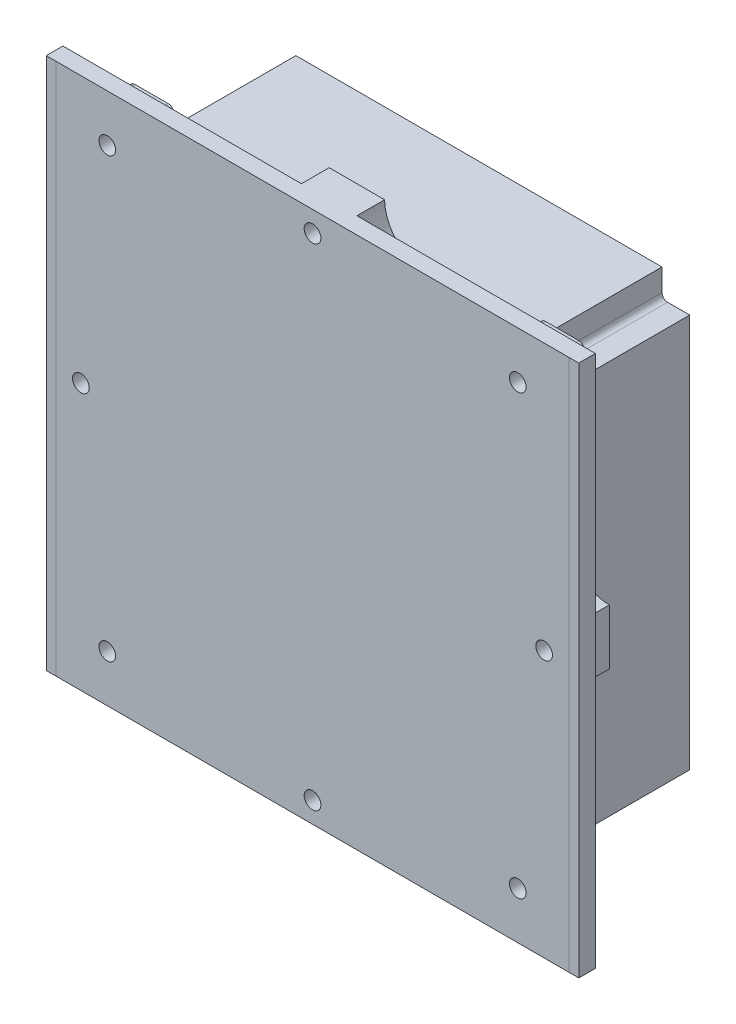
SolidWorks part; units mm, degrees
material "6061-T4 (SS)"
ref_plane "Front Plane" through (0, 0, 0) normal (0, 0, 1) x (1, 0, 0)
ref_plane "Top Plane" through (0, 0, 0) normal (0, 1, 0) x (1, 0, 0)
ref_plane "Right Plane" through (0, 0, 0) normal (1, 0, 0) x (0, 0, -1)
sketch "Sketch2" plane through (0, 0, 0) normal (0, 0, 1) x (1, 0, 0)
  line L1 (-48, 48) -> (48, 48)
  line L2 (-48, 48) -> (-48, -48)
  line L3 (-48, -48) -> (48, -48)
  line L4 (48, 48) -> (48, -48)
  point P4 (-48, 0)
  point P6 (0, -48)
  dimension "D1" = 96
extrude "Boss-Extrude1" add sketch "Sketch2" against normal blind 3 contours L1 L4 L3 L2
sketch "Sketch6" plane through (0, 0, -3) normal (0, 0, -1) x (-1, 0, 0)
  line L5 (-46.25, 48) -> (-46.25, -48)
  line L6 (-46.25, 48) -> (-46.25, -48)
  line L8 (46.25, 48) -> (46.25, -48)
  line L9 (46.25, 48) -> (46.25, -48)
  dimension "D1" = 1.75
  dimension "D2" = 1.75
split line "Split Line1"
sketch "Sketch3" plane through (0, 0, -3) normal (0, 0, -1) x (-1, 0, 0)
  line L0 (-35, 22.5) -> (-35, -22.5)
  line L1 (-20, -37.5) -> (20, -37.5)
  line L2 (35, 22.5) -> (35, -22.5)
  line L3 (-20, 37.5) -> (20, 37.5)
  line L4 (-31, -40.5) -> (31, -40.5)
  line L5 (38, 33.5) -> (38, -33.5)
  line L7 (-38, 33.5) -> (-38, -33.5)
  line L8 (-31, 40.5) -> (31, 40.5)
  line L9 (40, -35.5) -> (41.6953, -35.5) construction
  line L10 (33, -43.5) -> (41, -43.5)
  line L13 (41, -43.5) -> (41, -35.5)
  line L14 (35, -43.5) -> (41, -37.5) construction
  line L15 (0, 0) -> (0, -68.5412) construction
  line L16 (33, -42.5) -> (33, -44.6955) construction
  line L17 (0, 0) -> (-81.2569, 0) construction
  line L18 (40, -35.5) -> (41, -35.5)
  line L19 (33, -43.5) -> (33, -42.5)
  line L20 (38, -33.5) -> (38, -40.5) construction
  line L21 (38, -40.5) -> (31, -40.5) construction
  line L22 (-40, -35.5) -> (-41, -35.5)
  line L23 (-41, -43.5) -> (-41, -35.5)
  line L24 (-33, -43.5) -> (-41, -43.5)
  line L25 (-33, -43.5) -> (-33, -42.5)
  line L26 (40, 35.5) -> (41, 35.5)
  line L27 (41, 43.5) -> (41, 35.5)
  line L28 (33, 43.5) -> (41, 43.5)
  line L29 (33, 43.5) -> (33, 42.5)
  line L30 (-40, 35.5) -> (-41, 35.5)
  line L31 (-41, 43.5) -> (-41, 35.5)
  line L32 (-33, 43.5) -> (-41, 43.5)
  line L33 (-33, 43.5) -> (-33, 42.5)
  line L34 (-46.25, 48) -> (-46.25, -48) construction
  line L35 (46.25, 48) -> (-46.25, 48) construction
  arc A0 (-20, 37.5) -> (-35, 22.5) centre (-20, 22.5) ccw
  arc A1 (-20, -37.5) -> (-35, -22.5) centre (-20, -22.5) cw
  arc A2 (20, -37.5) -> (35, -22.5) centre (20, -22.5) ccw
  arc A3 (35, 22.5) -> (20, 37.5) centre (20, 22.5) ccw
  arc A6 (38, -33.5) -> (40, -35.5) centre (40, -33.5) ccw
  arc A7 (31, -40.5) -> (33, -42.5) centre (31, -42.5) cw
  arc A8 (-38, -33.5) -> (-40, -35.5) centre (-40, -33.5) cw
  arc A9 (-31, -40.5) -> (-33, -42.5) centre (-31, -42.5) ccw
  arc A10 (38, 33.5) -> (40, 35.5) centre (40, 33.5) cw
  arc A11 (31, 40.5) -> (33, 42.5) centre (31, 42.5) ccw
  arc A12 (-38, 33.5) -> (-40, 35.5) centre (-40, 33.5) ccw
  arc A13 (-31, 40.5) -> (-33, 42.5) centre (-31, 42.5) cw
  point P8 (0, -37.5)
  point P9 (0, 37.5)
  point P11 (-35, 0)
  point P12 (35, 0)
  dimension "D1" = 15
  dimension "D10" = 2
  dimension "D3" = 76
  dimension "D2" = 3
  dimension "D4" = 75
  dimension "D6" = 3
  dimension "D8" = 8
  dimension "D9" = 8
  dimension "D11" = 43.5
  dimension "D12" = 41
extrude "Boss-Extrude2" add sketch "Sketch3" along normal blind 27 contours L7 L5 L8
sketch "Sketch15" plane through (0, 0, -3) normal (0, 0, -1) x (-1, 0, 0)
  line L1 (46.25, 48) -> (-46.25, 48) construction
  line L2 (-5, 48) -> (5, 48)
  line L5 (31, 40.5) -> (-31, 40.5) construction
  line L6 (-12.5, 40.5) -> (12.5, 40.5)
  line L17 (45.5, 5) -> (45.5, -5)
  line L19 (38, 12.5) -> (38, -12.5)
  line L21 (5, -48) -> (-5, -48)
  line L23 (12.5, -40.5) -> (-12.5, -40.5)
  line L25 (-45.5, -5) -> (-45.5, 5)
  line L27 (-38, -12.5) -> (-38, 12.5)
  line L31 (38, -33.5) -> (38, 33.5) construction
  line L32 (-31, -40.5) -> (31, -40.5) construction
  line L34 (-38, 33.5) -> (-38, -33.5) construction
  arc A0 (5, 48) -> (12.5, 40.5) centre (12.5, 48) ccw
  arc A1 (-5, 48) -> (-12.5, 40.5) centre (-12.5, 48) cw
  arc A2 (45.5, 5) -> (38, 12.5) centre (45.5, 12.5) cw
  arc A7 (45.5, -5) -> (38, -12.5) centre (45.5, -12.5) ccw
  arc A14 (5, -48) -> (12.5, -40.5) centre (12.5, -48) cw
  arc A15 (-5, -48) -> (-12.5, -40.5) centre (-12.5, -48) ccw
  arc A23 (-38, 12.5) -> (-45.5, 5) centre (-45.5, 12.5) cw
  arc A25 (-38, -12.5) -> (-45.5, -5) centre (-45.5, -12.5) ccw
  point P6 (0, 40.5)
  point P17 (-38, 0)
  point P54 (38, 0)
  point P61 (0, -40.5)
  dimension "D2" = 10
  dimension "D5" = 7.5
  dimension "D6" = 10
  dimension "D8" = 7.5
  dimension "D11" = 7.5
extrude "Boss-Extrude6" add sketch "Sketch15" along normal blind 5
sketch "Sketch18" plane through (0, 0, 0) normal (0, 0, 1) x (1, 0, 0)
  line L0 (-5, 48) -> (5, 48) construction
  line L2 (-45.5, -5) -> (-45.5, 5) construction
  line L3 (45.5, 5) -> (45.5, -5) construction
  line L4 (5, -48) -> (-5, -48) construction
  circle A0 centre (0, 44.25) radius 1.5
  circle A1 centre (0, -44.25) radius 1.5
  circle A3 centre (41.75, 0) radius 1.5
  circle A7 centre (-41.75, 0) radius 1.5
  point P20 (0, 48)
  point P23 (45.5, 0)
  point P28 (-45.5, 0)
  point P30 (0, -48)
  dimension "D1" = 3
  dimension "D2" = 3.75
  dimension "D3" = 3.75
  dimension "D4" = 3.75
  dimension "D5" = 3.75
extrude "Cut-Extrude3" cut sketch "Sketch18" against normal through all contours A0
sketch "Sketch16" plane through (0, 0, -3) normal (0, 0, -1) x (-1, 0, 0)
  line L1 (-35, 22.5) -> (-30, 22.5)
  line L2 (-35, 22.5) -> (-35, 13)
  line L3 (-35, 13) -> (-30, 13)
  line L4 (-30, 22.5) -> (-30, 13)
  line L5 (30, 22.5) -> (35, 22.5)
  line L6 (30, 22.5) -> (30, 13)
  line L7 (30, 13) -> (35, 13)
  line L8 (35, 22.5) -> (35, 13)
  dimension "D1" = 9.5
  dimension "D2" = 5
  dimension "D3" = 5
extrude "Boss-Extrude7" add sketch "Sketch16" along normal blind 15 contours L4 L3 L2 L1
sketch "Sketch17" plane through (0, 0, -18) normal (0, 0, -1) x (-1, 0, 0)
  line L0 (-30, 13) -> (-30, 22.5) construction
  line L1 (-35, 13) -> (-30, 13) construction
  line L2 (30, 13) -> (35, 13) construction
  line L3 (30, 22.5) -> (30, 13) construction
  circle A0 centre (-32.5, 17.75) radius 1.5
  circle A1 centre (32.5, 17.75) radius 1.5
  point P7 (-30, 17.75)
  point P11 (-32.5, 13)
  point P15 (32.5, 13)
  point P18 (30, 17.75)
  dimension "D1" = 3
extrude "Cut-Extrude2" cut sketch "Sketch17" against normal blind 3.175 contours A0
fillet "Fillet2" radius 1 12 edges at (-33, 43.5, -16.5) (-41, 35.5, -16.5) (-41, 43.5, -16.5) (33, 43.5, -16.5) (41, 43.5, -16.5) (41, 35.5, -16.5) (41, -35.5, -16.5) (33, -43.5, -16.5) (-33, -43.5, -16.5) (-41, -35.5, -16.5) (-41, -43.5, -16.5) (41, -43.5, -16.5)
sketch "Sketch22" plane through (0, 0, 0) normal (0, 0, 1) x (1, 0, 0)
  line L0 (41, 42.5) -> (41, 36.5) construction
  line L1 (34, 43.5) -> (40, 43.5) construction
  line L2 (41, 42.5) -> (41, 36.5) construction
  line L3 (34, 43.5) -> (40, 43.5) construction
  line L4 (33.2929, 43.2071) -> (40.7071, 35.7929) construction
  line L5 (0, 0) -> (0, 60.4254) construction
  line L6 (0, 0) -> (75.1466, 0) construction
  arc A0 (31, 40.5) -> (33, 42.5) centre (31, 42.5) ccw construction
  arc A1 (34, 43.5) -> (33, 42.5) centre (34, 42.5) ccw construction
  arc A2 (40, 35.5) -> (38, 33.5) centre (40, 33.5) ccw construction
  arc A3 (40, 35.5) -> (41, 36.5) centre (40, 36.5) ccw construction
  arc A4 (41, 42.5) -> (40, 43.5) centre (40, 42.5) ccw construction
  arc A5 (31, 40.5) -> (33, 42.5) centre (31, 42.5) ccw construction
  arc A6 (34, 43.5) -> (33, 42.5) centre (34, 42.5) ccw construction
  arc A7 (40, 35.5) -> (38, 33.5) centre (40, 33.5) ccw construction
  arc A8 (40, 35.5) -> (41, 36.5) centre (40, 36.5) ccw construction
  arc A9 (41, 42.5) -> (40, 43.5) centre (40, 42.5) ccw construction
  circle A10 centre (37, 39.5) radius 1.5
  circle A11 centre (-37, 39.5) radius 1.5
  circle A12 centre (37, -39.5) radius 1.5
  circle A13 centre (-37, -39.5) radius 1.5
  dimension "D1" = 3
extrude "Cut-Extrude5" cut sketch "Sketch22" against normal through all
sketch "Sketch23" plane through (0, 0, -30) normal (0, 0, -1) x (-1, 0, 0)
  line L0 (-40.7071, -43.2071) -> (-32.5482, -35.0482) construction
  line L1 (-40, -35.5) -> (-34, -35.5)
  line L2 (-33, -36.5) -> (-33, -42.5)
  line L3 (-41, -36.5) -> (-41, -42.5) construction
  line L4 (-40, -43.5) -> (-34, -43.5) construction
  line L5 (-41, -36.5) -> (-41, -42.5)
  line L6 (-40, -43.5) -> (-34, -43.5)
  line L7 (0, 0) -> (0, -60.8456) construction
  line L8 (0, 0) -> (68.1956, 0) construction
  line L9 (-41, -42.5) -> (-41, -36.5)
  line L10 (-34, -43.5) -> (-40, -43.5)
  line L11 (-34, -35.5) -> (-40, -35.5)
  line L12 (-33, -42.5) -> (-33, -36.5)
  line L13 (40.7071, -43.2071) -> (32.5482, -35.0482) construction
  line L14 (33, -42.5) -> (33, -36.5)
  line L15 (34, -35.5) -> (40, -35.5)
  line L16 (34, -43.5) -> (40, -43.5)
  line L17 (41, -42.5) -> (41, -36.5)
  line L18 (40, -43.5) -> (34, -43.5)
  line L19 (41, -36.5) -> (41, -42.5)
  line L20 (33, -36.5) -> (33, -42.5)
  line L21 (40, -35.5) -> (34, -35.5)
  line L22 (40.7071, 43.2071) -> (32.5482, 35.0482) construction
  line L23 (40, 35.5) -> (34, 35.5)
  line L24 (33, 36.5) -> (33, 42.5)
  line L25 (41, 36.5) -> (41, 42.5)
  line L26 (40, 43.5) -> (34, 43.5)
  line L27 (41, 42.5) -> (41, 36.5)
  line L28 (34, 43.5) -> (40, 43.5)
  line L29 (34, 35.5) -> (40, 35.5)
  line L30 (33, 42.5) -> (33, 36.5)
  line L31 (-40.7071, 43.2071) -> (-32.5482, 35.0482) construction
  line L32 (-33, 42.5) -> (-33, 36.5)
  line L33 (-34, 35.5) -> (-40, 35.5)
  line L34 (-34, 43.5) -> (-40, 43.5)
  line L35 (-41, 42.5) -> (-41, 36.5)
  line L36 (-40, 43.5) -> (-34, 43.5)
  line L37 (-41, 36.5) -> (-41, 42.5)
  line L38 (-33, 36.5) -> (-33, 42.5)
  line L39 (-40, 35.5) -> (-34, 35.5)
  arc A0 (-41, -42.5) -> (-40, -43.5) centre (-40, -42.5) ccw construction
  arc A1 (-40, -35.5) -> (-41, -36.5) centre (-40, -36.5) ccw construction
  arc A2 (-34, -43.5) -> (-33, -42.5) centre (-34, -42.5) ccw construction
  arc A3 (-40, -35.5) -> (-41, -36.5) centre (-40, -36.5) ccw
  arc A4 (-41, -42.5) -> (-40, -43.5) centre (-40, -42.5) ccw
  arc A5 (-34, -43.5) -> (-33, -42.5) centre (-34, -42.5) ccw
  arc A6 (-34, -35.5) -> (-33, -36.5) centre (-34, -36.5) cw
  arc A7 (-41, -36.5) -> (-40, -35.5) centre (-40, -36.5) cw
  arc A8 (-33, -42.5) -> (-34, -43.5) centre (-34, -42.5) cw
  arc A9 (33, -42.5) -> (34, -43.5) centre (34, -42.5) ccw
  arc A10 (41, -36.5) -> (40, -35.5) centre (40, -36.5) ccw
  arc A11 (34, -35.5) -> (33, -36.5) centre (34, -36.5) ccw
  arc A12 (34, -43.5) -> (33, -42.5) centre (34, -42.5) cw
  arc A13 (41, -42.5) -> (40, -43.5) centre (40, -42.5) cw
  arc A14 (40, -35.5) -> (41, -36.5) centre (40, -36.5) cw
  arc A15 (40, 35.5) -> (41, 36.5) centre (40, 36.5) ccw
  arc A16 (41, 42.5) -> (40, 43.5) centre (40, 42.5) ccw
  arc A17 (34, 43.5) -> (33, 42.5) centre (34, 42.5) ccw
  arc A18 (34, 35.5) -> (33, 36.5) centre (34, 36.5) cw
  arc A19 (41, 36.5) -> (40, 35.5) centre (40, 36.5) cw
  arc A20 (33, 42.5) -> (34, 43.5) centre (34, 42.5) cw
  arc A21 (-33, 42.5) -> (-34, 43.5) centre (-34, 42.5) ccw
  arc A22 (-41, 36.5) -> (-40, 35.5) centre (-40, 36.5) ccw
  arc A23 (-34, 35.5) -> (-33, 36.5) centre (-34, 36.5) ccw
  arc A24 (-34, 43.5) -> (-33, 42.5) centre (-34, 42.5) cw
  arc A25 (-41, 42.5) -> (-40, 43.5) centre (-40, 42.5) cw
  arc A26 (-40, 35.5) -> (-41, 36.5) centre (-40, 36.5) cw
  point P16 (-33, -35.5)
  point P35 (33, -35.5)
  point P50 (33, 35.5)
  point P65 (-33, 35.5)
  circle M6 centre (37, 39.5) radius 1.5
  circle M7 centre (-37, -39.5) radius 1.5
  circle M8 centre (37, -39.5) radius 1.5
  circle M9 centre (-37, 39.5) radius 1.5
  line M10 (40, 43.5) -> (34, 43.5)
  arc M11 (34, 43.5) -> (33, 42.5) centre (34, 42.5) ccw
  arc M15 (-33, 42.5) -> (-34, 43.5) centre (-34, 42.5) ccw
  line M16 (-34, 43.5) -> (-40, 43.5)
  arc M17 (-40, 43.5) -> (-41, 42.5) centre (-40, 42.5) ccw
  line M18 (-41, 42.5) -> (-41, 36.5)
  arc M19 (-41, 36.5) -> (-40, 35.5) centre (-40, 36.5) ccw
  arc M23 (-40, -35.5) -> (-41, -36.5) centre (-40, -36.5) ccw
  line M24 (-41, -36.5) -> (-41, -42.5)
  arc M25 (-41, -42.5) -> (-40, -43.5) centre (-40, -42.5) ccw
  line M26 (-40, -43.5) -> (-34, -43.5)
  arc M27 (-34, -43.5) -> (-33, -42.5) centre (-34, -42.5) ccw
  arc M31 (33, -42.5) -> (34, -43.5) centre (34, -42.5) ccw
  line M32 (34, -43.5) -> (40, -43.5)
  arc M33 (40, -43.5) -> (41, -42.5) centre (40, -42.5) ccw
  line M34 (41, -42.5) -> (41, -36.5)
  arc M35 (41, -36.5) -> (40, -35.5) centre (40, -36.5) ccw
  arc M39 (40, 35.5) -> (41, 36.5) centre (40, 36.5) ccw
  line M40 (41, 36.5) -> (41, 42.5)
  arc M41 (41, 42.5) -> (40, 43.5) centre (40, 42.5) ccw
  dimension "D1" = 1
extrude "Cut-Extrude6" cut sketch "Sketch23" against normal up to surface (22 mm away) contours A18 L23 L24 M39 M40 M41 M10 M11 M6 | L33 A23 L32 M15 M16 M17 M18 M19 M9 | A6 L1 L2 M23 M24 M25 M26 M27 M7 | L15 A11 L14 M31 M32 M33 M34 M35 M8
sketch "Sketch24" plane through (0, 0, -30) normal (0, 0, -1) x (-1, 0, 0)
  line L0 (-38, 33.5) -> (-38, -33.5) construction
  line L1 (38, 40.5) -> (-38, 40.5)
  line L2 (38, 40.5) -> (38, -40.5)
  line L3 (38, -40.5) -> (-38, -40.5)
  line L4 (-38, 40.5) -> (-38, -40.5)
  line L5 (38, 40.5) -> (-38, -40.5) construction
  line L6 (38, -40.5) -> (-38, 40.5) construction
  line L7 (-31, -40.5) -> (31, -40.5) construction
  line L12 (41, -43.5) -> (-41, -43.5)
  line L13 (-41, 43.5) -> (-41, -43.5)
  line L14 (41, 43.5) -> (-41, 43.5)
  line L15 (41, 43.5) -> (41, -43.5)
  point P0 (0, 0)
  dimension "D1" = 3
extrude "Cut-Extrude8" cut sketch "Sketch24" against normal up to surface (22 mm away) up to face at (40.25, 0, -8)
